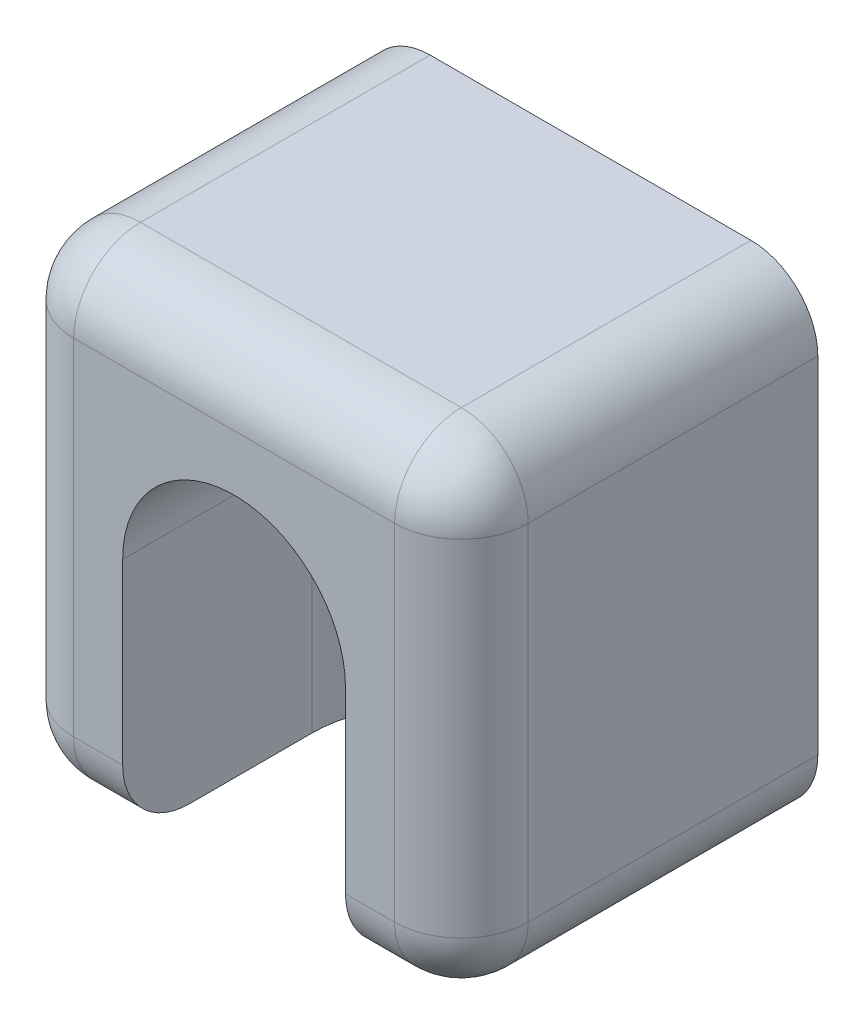
SolidWorks part; units mm, degrees
note: '?' marks a value the reader was unsure of.
ref_plane "Front Plane" through (0, 0, 0) normal (0, 0, 1) x (1, 0, 0)
ref_plane "Top Plane" through (0, 0, 0) normal (0, 1, 0) x (1, 0, 0)
ref_plane "Right Plane" through (0, 0, 0) normal (1, 0, 0) x (0, 0, -1)
ref_plane "Body alignment" through (0, 0, -6) normal (0, 0, 1) x (1, 0, 0)
ref_plane "Vertical center" through (10.2, 0, 0) normal (1, 0, 0) x (0, 0, -1)
ref_plane "Horizontal plane" through (0, 10.75, 0) normal (0, 1, 0) x (-1, 0, 0)
sketch "Sketch1" plane through (0, 0, 0) normal (0, 0, 1) x (1, 0, 0)
  line L1 (0, 0) -> (20.4, 0)
  line L2 (0, 0) -> (0, 21.5)
  line L3 (0, 21.5) -> (20.4, 21.5)
  line L4 (20.4, 0) -> (20.4, 21.5)
  dimension "D1" = 20.4
  dimension "D2" = 21.5
extrude "Extrude1" add sketch "Sketch1" against normal blind 16
fillet "Fillet8" radius 3 8 edges at (20.4, 10.75, 0) (10.2, 0, 0) (0, 10.75, 0) (10.2, 21.5, 0) (20.4, 0, -8) (20.4, 21.5, -8) (0, 21.5, -8) (0, 0, -8)
ref_axis "Center axis" through (10.2, 10.75, 0.8) along (0, 0, -1)?
sketch "Sketch2" plane through (10.2, 0, 0) normal (1, 0, 0) x (0, 0, -1)
  line L0 (0, 3) -> (0, 18.5) construction
  line L1 (-1, 16) -> (13.5, 16)
  line L2 (-1, 16) -> (-1, -1)
  line L3 (-1, -1) -> (13.5, -1)
  line L4 (13.5, 16) -> (13.5, -1)
  line L5 (16, 0) -> (3, 0) construction
  dimension "D1" = 1
  dimension "D2" = 1
  dimension "D3" = 17
  dimension "D4" = 14.5
extrude "Extrude2" cut sketch "Sketch2" against normal mid plane 10
fillet "Fillet9" radius 5 4 edges at (10.2, 16, 0) (5.2, 16, -6.75) (10.2, 16, -13.5) (15.2, 16, -6.75)
fillet "Fillet10" radius 5 4 edges at (10.2, 0, -13.5) (5.2, 5.5, -13.5) (15.2, 5.5, -13.5) (10.2, 16, -13.5)
